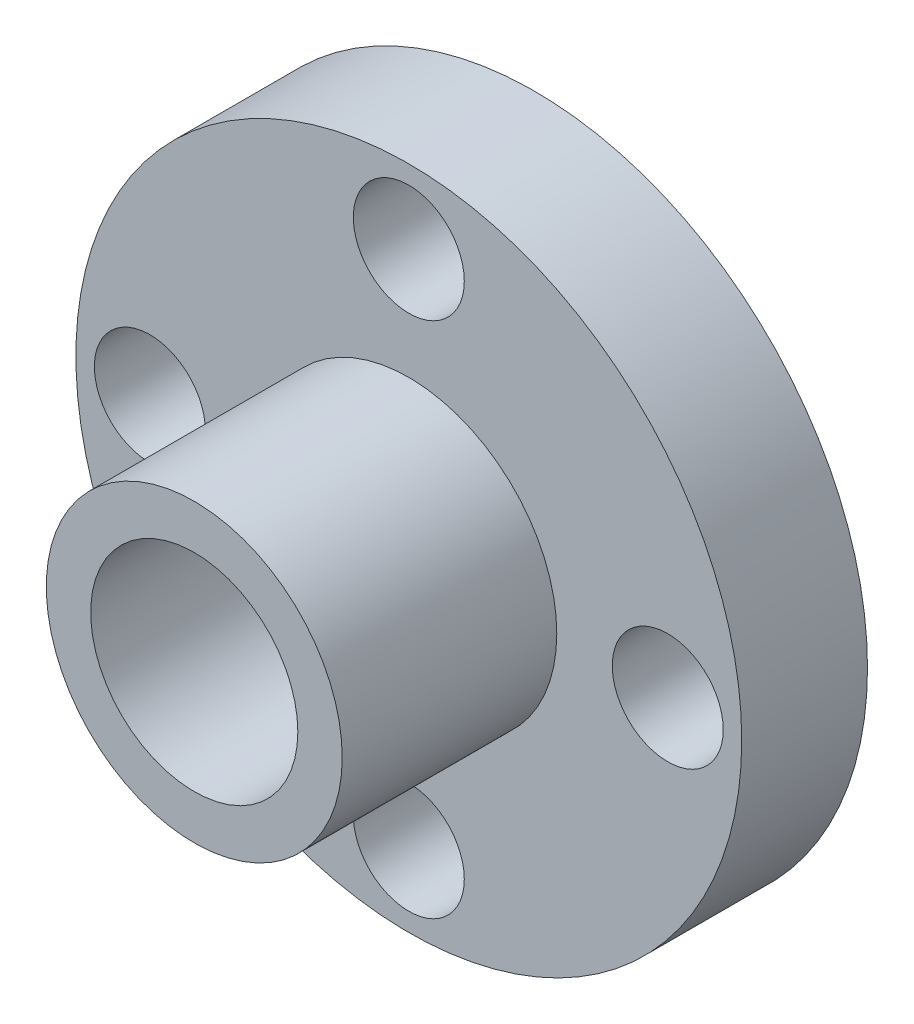
SolidWorks part; units mm, degrees
ref_plane "Front Plane" through (0, 0, 0) normal (0, 0, 1) x (1, 0, 0)
ref_plane "Top Plane" through (0, 0, 0) normal (0, 1, 0) x (1, 0, 0)
ref_plane "Right Plane" through (0, 0, 0) normal (1, 0, 0) x (0, 0, -1)
sketch "Sketch1" plane through (0, 0, 0) normal (1, 0, 0) x (0, 0, -1)
  line L0 (-277.2967, 0) -> (234.0909, 0) construction
  line L5 (0, 0) -> (85, 0)
  line L6 (0, 0) -> (0, 225)
  line L11 (0, 225) -> (85, 225)
  line L12 (85, 0) -> (85, 225)
  line L13 (0, 0) -> (85, 225) construction
  line L14 (0, 225) -> (85, 0) construction
  line L15 (0, 0) -> (-145, 0)
  line L16 (0, 0) -> (0, 100)
  line L17 (0, 100) -> (-145, 100)
  line L18 (-145, 0) -> (-145, 100)
  line L19 (0, 0) -> (-145, 100) construction
  line L20 (0, 100) -> (-145, 0) construction
  point P4 (42.5, 112.5)
  point P8 (-72.5, 50)
  dimension "D1" = 230
  dimension "D2" = 85
revolve "Revolve1" add sketch "Sketch1" angle 360 about L0 region at (0, 112.5, -42.5) region at (0, 50, 72.5)
sketch "Sketch2" plane through (0, 0, 145) normal (0, 0, 1) x (1, 0, 0)
  line L0 (0, 299.5046) -> (0, -258.5913) construction
  line L1 (-323.1392, 0) -> (377.9237, 0) construction
  circle A0 centre (0, 0) radius 70
  dimension "D1" = 140
extrude "Cut-Extrude1" cut sketch "Sketch2" against normal blind 230 contours A0
sketch "Sketch3" plane through (0, 0, 0) normal (0, 0, 1) x (1, 0, 0)
  line L0 (0, 284.7446) -> (0, -257.2126) construction
  line L1 (-310.1079, 0) -> (344.2598, 0) construction
  circle A2 centre (0, 175) radius 37.5
  circle A3 centre (175, 0) radius 37.5
  circle A4 centre (0, -175) radius 37.5
  circle A5 centre (-175, 0) radius 37.5
  point P14 (0, 0)
  dimension "D1" = 90
  dimension "D2" = 75
  dimension "D3" = 4
other "AlignGroup1"
extrude "Cut-Extrude3" cut sketch "Sketch3" against normal through all contours A2 | A5 | A3 | A4
